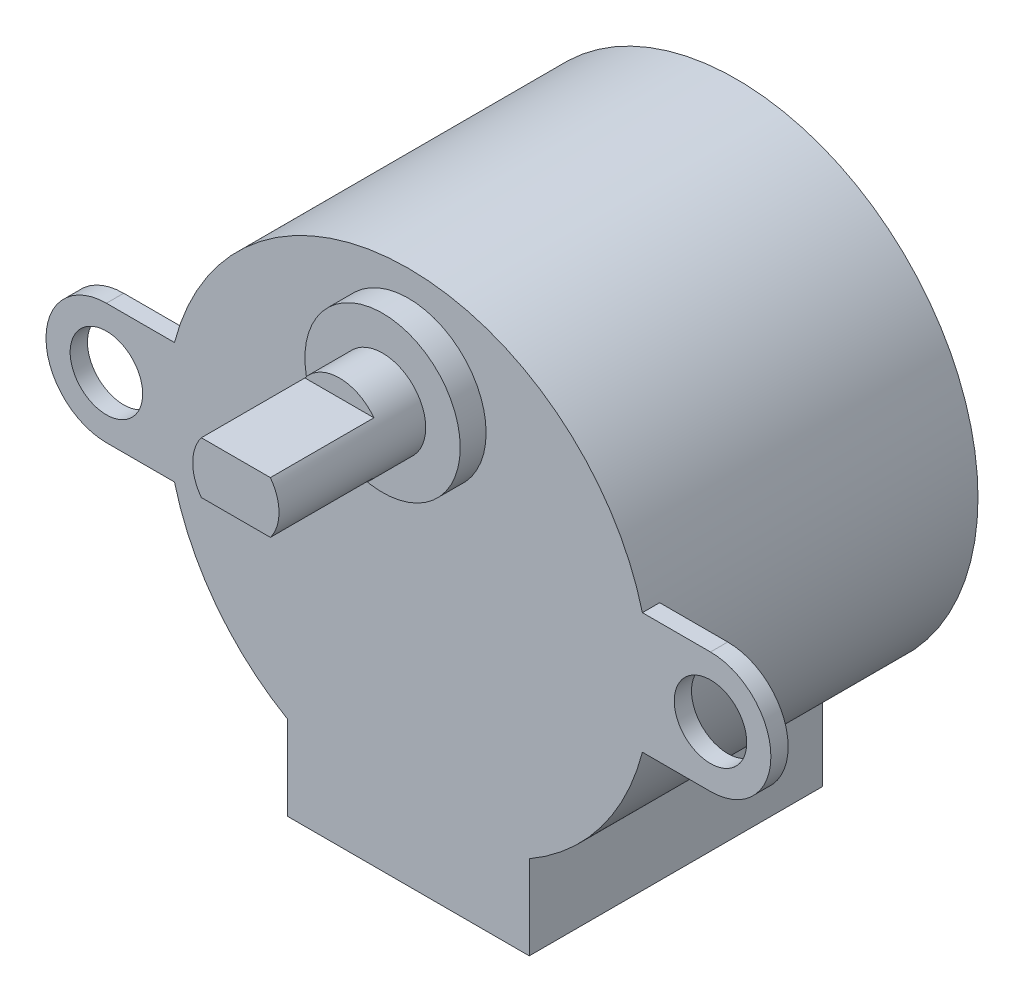
SolidWorks part; units mm, degrees
ref_plane "Front Plane" through (0, 0, 0) normal (0, 0, 1) x (1, 0, 0)
ref_plane "Top Plane" through (0, 0, 0) normal (0, 1, 0) x (1, 0, 0)
ref_plane "Right Plane" through (0, 0, 0) normal (1, 0, 0) x (0, 0, -1)
sketch "Sketch2" plane through (0, 0, 0) normal (0, 0, 1) x (1, 0, 0)
  circle A0 centre (0, 0) radius 14
  dimension "D1" = 28
extrude "Boss-Extrude1" add sketch "Sketch2" along normal blind 19
sketch "Sketch3" plane through (0, 0, 19) normal (0, 0, 1) x (1, 0, 0)
  circle A0 centre (0, 8) radius 4.5
  circle A1 centre (0, 0) radius 14 construction
  circle A2 centre (0, 8) radius 2.5
  dimension "D1" = 9
  dimension "D2" = 8
  dimension "D3" = 5
extrude "Boss-Extrude2" add sketch "Sketch3" along normal blind 4 contours A2 region at (0, 8, 19)
extrude "Boss-Extrude3" add sketch "Sketch3<3>" along normal blind 1.5 contours A0
sketch "Sketch3<3>" plane through (0, 0, 19) normal (0, 0, 1) x (1, 0, 0) same geometry as "Sketch3"
sketch "Sketch4" plane through (0, 0, 23) normal (0, 0, 1) x (1, 0, 0)
  line L1 (-2, 9.5) -> (2, 9.5)
  line L3 (-2, 6.5) -> (2, 6.5)
  line L5 (-2, 9.5) -> (2, 6.5) construction
  line L6 (-2, 6.5) -> (2, 9.5) construction
  circle A0 centre (0, 8) radius 2.5 construction
  arc A1 (-2, 9.5) -> (-2, 6.5) centre (0, 8) ccw
  arc A2 (2, 9.5) -> (2, 6.5) centre (0, 8) cw
  point P0 (0, 8)
  dimension "D1" = 3
extrude "Boss-Extrude4" add sketch "Sketch4" along normal blind 6 contours L3 A2 L1 A1
sketch "Sketch6" plane through (0, 0, 19) normal (0, 0, 1) x (1, 0, 0)
  line L0 (-7, 0) -> (7, 0)
  line L2 (-7, 0) -> (-7, -17)
  line L3 (-7, -17) -> (7, -17)
  line L4 (7, 0) -> (7, -17)
  point P0 (0, 0)
  dimension "D1" = 14
  dimension "D2" = 17
extrude "Boss-Extrude5" add sketch "Sketch6" against normal blind 17 contours L4 L3 L2 L0
sketch "Sketch7" plane through (0, 0, 19) normal (0, 0, 1) x (1, 0, 0)
  line L1 (-17.5, 3.5) -> (17.5, 3.5)
  line L3 (-17.5, -3.5) -> (17.5, -3.5)
  arc A0 (-17.5, 3.5) -> (-17.5, -3.5) centre (-17.5, 0) ccw
  arc A1 (17.5, -3.5) -> (17.5, 3.5) centre (17.5, 0) ccw
  circle A2 centre (-17.5, 0) radius 2.1
  circle A3 centre (17.5, 0) radius 2.1
  point P0 (0, 0)
  dimension "D2" = 4.2
  dimension "D3" = 4.2
  dimension "D1" = 7
extrude "Boss-Extrude6" add sketch "Sketch7" against normal blind 1
